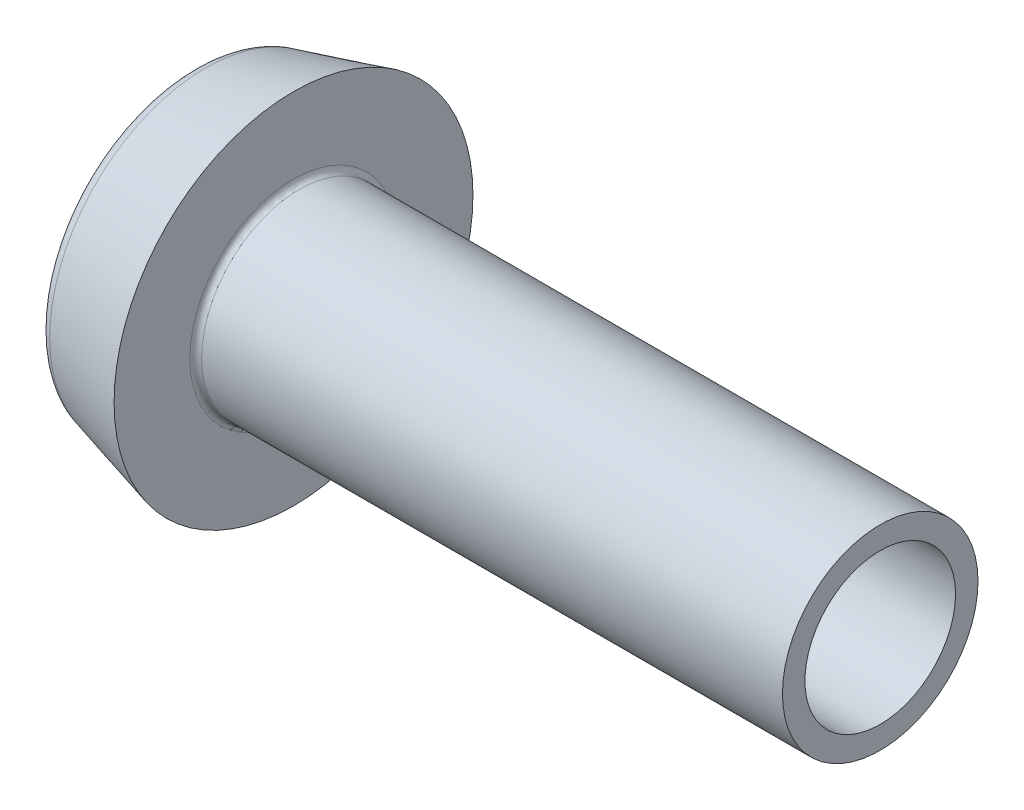
SolidWorks part; units mm, degrees
ref_plane "Front" through (0, 0, 0) normal (0, 0, 1) x (1, 0, 0)
ref_plane "Top" through (0, 0, 0) normal (0, 1, 0) x (1, 0, 0)
ref_plane "Right" through (0, 0, 0) normal (1, 0, 0) x (0, 0, -1)
sketch "Sketch1" plane through (0, 0, 0) normal (0, 0, 1) x (1, 0, 0)
  line L0 (-47.217, 0) -> (5.8534, 0) construction
  line L1 (35.24, 0) -> (35.24, 5)
  line L2 (35.24, 5) -> (5.54, 5)
  line L3 (5.24, 5.3) -> (5.24, 9.175)
  line L4 (5.24, 9.175) -> (0.7412, 7.9695)
  line L5 (0, 7.0036) -> (0, 0)
  line L6 (35.24, 0) -> (0, 0)
  arc A0 (5.54, 5) -> (5.24, 5.3) centre (5.54, 5.3) cw
  arc A1 (0.7412, 7.9695) -> (0, 7.0036) centre (1, 7.0036) ccw
  point P11 (5.24, 5)
  dimension "r" = 0.3
  dimension "r1" = 1
  dimension "D1" = 15
  dimension "d" = 10
  dimension "dk" = 18.35
  dimension "K" = 5.24
  dimension "l" = 30
revolve "Base-Revolve" add sketch "Sketch1" angle 360 about L0
sketch "Sketch2" plane through (0, 0, 0) normal (0, 0, 1) x (1, 0, 0)
  line L0 (1.3562, 0) -> (-19.7528, 0) construction
  line L2 (35.24, 0) -> (35.24, 3.85)
  line L4 (35.24, 3.85) -> (25.61, 3.85)
  line L5 (25.61, 3.85) -> (22.8128, 0)
  line L6 (35.24, 0) -> (22.8128, 0)
  line L7 (35.24, -5) -> (35.24, 5) construction
  dimension "dt" = 7.7
  dimension "D2" = 54
  dimension "t" = 9.63
revolve "Cut-Revolve1" cut sketch "Sketch2" angle 360 about L0
